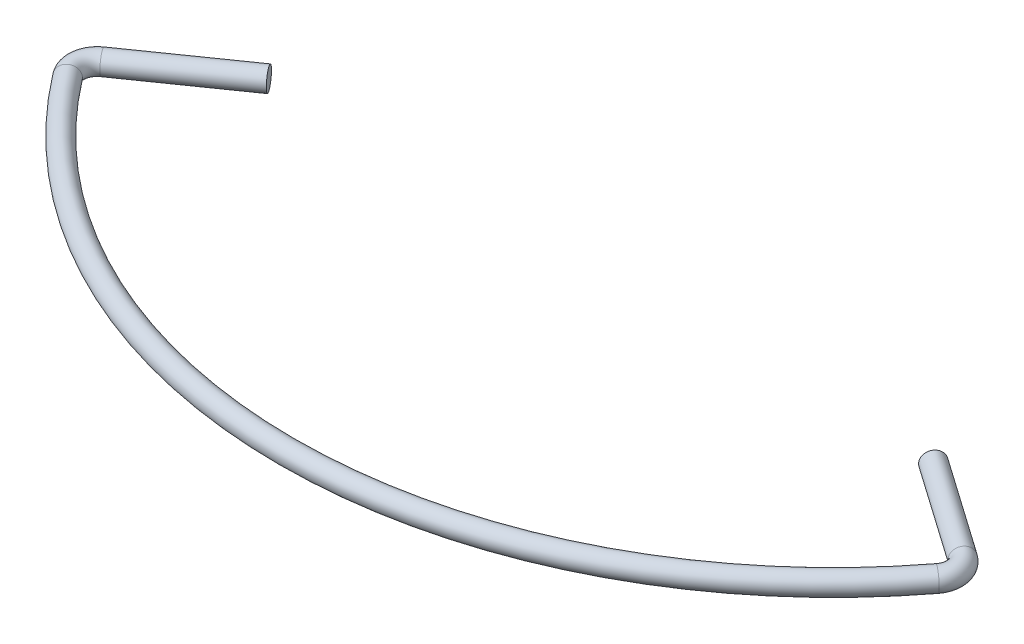
SolidWorks part; units mm, degrees
ref_plane "Front Plane" through (0, 0, 0) normal (0, 0, 1) x (1, 0, 0)
ref_plane "Top Plane" through (0, 0, 0) normal (0, 1, 0) x (1, 0, 0)
ref_plane "Right Plane" through (0, 0, 0) normal (1, 0, 0) x (0, 0, -1)
sketch "Overhead Sketch" plane through (0, 0, 0) normal (0, 1, 0) x (1, 0, 0)
  line L0 (0, 675) -> (0, -675) construction
  line L1 (0, 0) -> (552.9276, -387.1641) construction
  line L2 (0, 0) -> (-552.9276, -387.1641) construction
  line L3 (552.9276, -387.1641) -> (609.7733, -426.9678)
  line L4 (-552.9276, -387.1641) -> (-609.7733, -426.9678)
  line L5 (771.339, -75.2403) -> (334.5162, -699.0879) construction
  circle A0 centre (0, 0) radius 675 construction
  arc A1 (-616.4277, -469.7253) -> (616.4277, -469.7253) centre (0, 0) ccw
  arc A2 (-616.4277, -469.7253) -> (-609.7733, -426.9678) centre (-592.566, -451.5424) cw
  arc A3 (609.7733, -426.9678) -> (616.4277, -469.7253) centre (592.566, -451.5424) cw
  point P11 (-634.8428, -444.5217)
  point P14 (634.8428, -444.5217)
  point P17 (552.9276, -387.1641)
  dimension "D1" = 1350
  dimension "D3" = 30
  dimension "D4" = 100
  dimension "D2" = 110
ref_plane "Reference Plane" through (0, 0, 387.1641) normal (0, 0, 1) x (1, 0, 0)
sketch "Plane Definition Sketch" plane through (0, 0, 387.1641) normal (0, 0, 1) x (1, 0, 0)
  line L0 (552.9276, 50) -> (552.9276, -50) construction
  point P2 (552.9276, 0)
  dimension "D1" = 100
ref_plane "Cross Section Plane" through (552.9276, 0, 387.1641) normal (0.8192, 0, 0.5736) x (0.5736, 0, -0.8192)
sketch "Left Cross Section Sketch" plane through (552.9276, 0, 387.1641) normal (0.8192, 0, 0.5736) x (0.5736, 0, -0.8192)
  circle A0 centre (0, 0) radius 15
  dimension "D1" = 30
sweep "Bar Sweep" add profiles "Left Cross Section Sketch" path "Overhead Sketch"
sketch "Right Cross Section Sketch" plane through (-552.9276, 0, 387.1641) normal (0.8192, 0, -0.5736) x (-0.5736, 0, -0.8192)
  circle A0 centre (0, 0) radius 15
  circle A1 centre (0, 0) radius 15 construction
extrude "Right Joint Extrude" add sketch "Right Cross Section Sketch" along normal blind 100
extrude "Left Joint Extrude" add sketch "Left Cross Section Sketch<2>" against normal blind 100
sketch "Left Cross Section Sketch<2>" plane through (552.9276, 0, 387.1641) normal (0.8192, 0, 0.5736) x (0.5736, 0, -0.8192) same geometry as "Left Cross Section Sketch"
